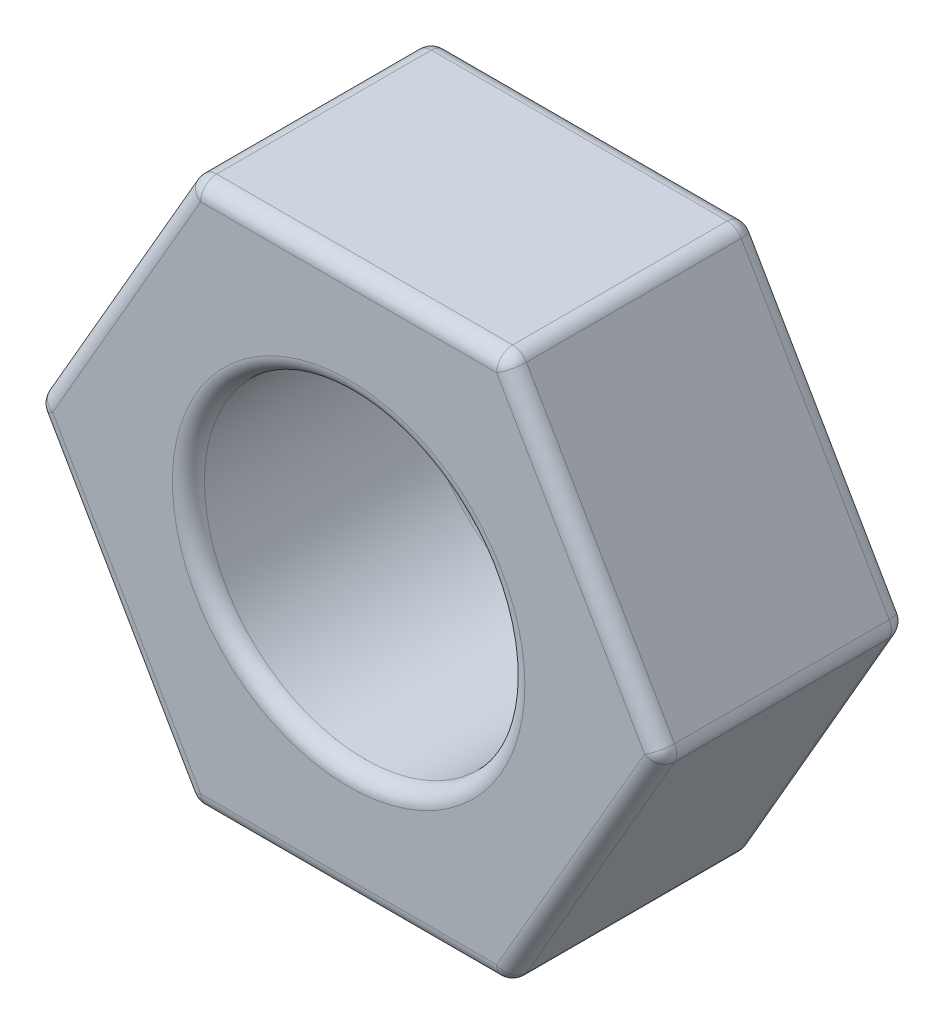
SolidWorks part; units mm, degrees
material "1023 Kohlenstoffstahlblech (SS)"
ref_plane "Ebene vorne" through (0, 0, 0) normal (0, 0, 1) x (1, 0, 0)
ref_plane "Ebene oben" through (0, 0, 0) normal (0, 1, 0) x (1, 0, 0)
ref_plane "Ebene rechts" through (0, 0, 0) normal (1, 0, 0) x (0, 0, -1)
sketch "Skizze1" plane through (0, 0, 0) normal (0, 0, 1) x (1, 0, 0)
  line L1 (-9.815, 0) -> (-4.9075, -8.5)
  line L2 (-4.9075, -8.5) -> (4.9075, -8.5)
  line L3 (4.9075, -8.5) -> (9.815, 0)
  line L4 (9.815, 0) -> (4.9075, 8.5)
  line L5 (4.9075, 8.5) -> (-4.9075, 8.5)
  line L6 (-4.9075, 8.5) -> (-9.815, 0)
  circle A0 centre (0, 0) radius 8.5 construction
  circle A1 centre (0, 0) radius 5
  dimension "D1" = 17
  dimension "D2" = 10
extrude "Aufsatz-Linear austragen1" add sketch "Skizze1" along normal mid plane 7.7
ref_axis "Achse1" through (0, 0, 3.85) along (0, 0, -1)
fillet "Verrundung1" radius 0.5 20 edges at (-4.9075, 8.5, 0) (4.9075, 8.5, 0) (9.815, 0, 0) (4.9075, -8.5, 0) (-4.9075, -8.5, 0) (-9.815, 0, 0) (0, 8.5, 3.85) (7.3612, 4.25, 3.85) (7.3612, -4.25, 3.85) (0, -8.5, 3.85) (-7.3612, -4.25, 3.85) (-7.3612, 4.25, 3.85) (0, 8.5, -3.85) (7.3612, 4.25, -3.85) (7.3612, -4.25, -3.85) (0, -8.5, -3.85) (-7.3612, -4.25, -3.85) (-7.3612, 4.25, -3.85) (5, 0, 3.85) (5, 0, -3.85)
